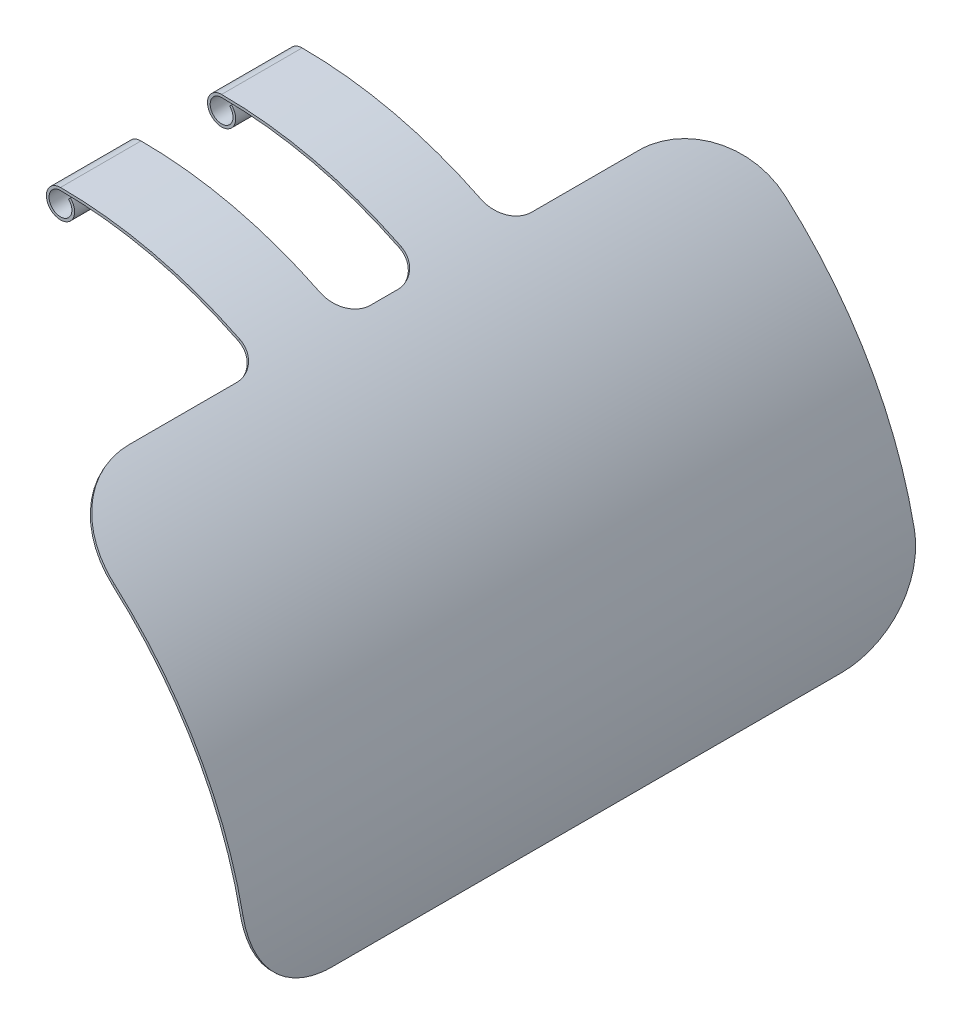
SolidWorks part; units mm, degrees
material "1.4301 (X5CrNi18-10)"
ref_plane "Front Plane" through (0, 0, 0) normal (0, 0, 1) x (1, 0, 0)
ref_plane "Top Plane" through (0, 0, 0) normal (0, 1, 0) x (1, 0, 0)
ref_plane "Right Plane" through (0, 0, 0) normal (1, 0, 0) x (0, 0, -1)
sketch "Sketch2" plane through (0, 0, 0) normal (0, 0, 1) x (1, 0, 0)
  line L0 (0, -55) -> (0, 55) construction
  line L1 (0, 0) -> (0, 175.478) construction
  line L2 (-60.0259, 0) -> (145.2452, 0) construction
  line L4 (0, 145.75) -> (4.6775, 150.4275) construction
  line L5 (3.0052, 148.7552) -> (3.7123, 149.4623)
  line L7 (0, 0) -> (136.1579, 0) construction
  line L8 (55, 0) -> (-55, 0) construction
  line L9 (150, 0) -> (151, 0)
  arc A0 (150, 0) -> (0, 150) centre (0, 0) ccw
  arc A1 (0, 150) -> (3.0052, 148.7552) centre (0, 145.75) ccw
  arc A2 (151, 0) -> (0, 151) centre (0, 0) ccw
  arc A3 (0, 151) -> (3.7123, 149.4623) centre (0, 145.75) ccw
  arc A4 (150, 0) -> (0, 150) centre (0, 0) ccw construction
  arc A5 (151, 0) -> (0, 151) centre (0, 0) ccw construction
  dimension "D1" = 300
  dimension "D2" = 8.5
  dimension "D3" = 45
  dimension "D5" = 0
  dimension "D4" = 1
extrude "Boss-Extrude1" add sketch "Sketch2" along normal mid plane 250
sketch "Sketch3" plane through (0, 0, 0) normal (0, 0, 1) x (1, 0, 0)
  line L0 (75, 129.9038) -> (75.5, 130.7698)
  line L1 (55, 0) -> (-55, 0) construction
  line L2 (150, 0) -> (151, 0)
  line L3 (3.7123, 149.4623) -> (3.0052, 148.7552)
  line L5 (3.7123, 149.4623) -> (3.0052, 148.7552)
  arc A4 (0, 150) -> (3.0052, 148.7552) centre (0, 145.75) ccw
  arc A5 (150, 0) -> (0, 150) centre (0, 0) ccw
  arc A6 (151, 0) -> (0, 151) centre (0, 0) ccw
  arc A7 (0, 151) -> (3.7123, 149.4623) centre (0, 145.75) ccw
  arc A8 (0, 150) -> (3.0052, 148.7552) centre (0, 145.75) ccw
  arc A9 (75, 129.9038) -> (0, 150) centre (0, 0) ccw
  arc A10 (75.5, 130.7698) -> (0, 151) centre (0, 0) ccw
  arc A11 (0, 151) -> (3.7123, 149.4623) centre (0, 145.75) ccw
  dimension "D2" = 60
  dimension "D1" = 0
extrude "Cut-Extrude1" cut sketch "Sketch3" against normal mid plane 30
sketch "Sketch4" plane through (0, 0, 125) normal (0, 0, 1) x (1, 0, 0)
  line L0 (75, 129.9038) -> (75.5, 130.7698)
  line L1 (55, 0) -> (-55, 0) construction
  line L2 (150, 0) -> (151, 0)
  line L3 (3.7123, 149.4623) -> (3.0052, 148.7552)
  line L5 (3.7123, 149.4623) -> (3.0052, 148.7552)
  arc A4 (0, 150) -> (3.0052, 148.7552) centre (0, 145.75) ccw
  arc A5 (150, 0) -> (0, 150) centre (0, 0) ccw
  arc A6 (151, 0) -> (0, 151) centre (0, 0) ccw
  arc A7 (0, 151) -> (3.7123, 149.4623) centre (0, 145.75) ccw
  arc A8 (0, 150) -> (3.0052, 148.7552) centre (0, 145.75) ccw
  arc A9 (75, 129.9038) -> (0, 150) centre (0, 0) ccw
  arc A10 (75.5, 130.7698) -> (0, 151) centre (0, 0) ccw
  arc A11 (0, 151) -> (3.7123, 149.4623) centre (0, 145.75) ccw
  dimension "D2" = 60
  dimension "D1" = 0
extrude "Cut-Extrude2" cut sketch "Sketch4" against normal blind 80
mirror "Mirror1" about plane through (0, 0, 0) normal (0, 0, 1) of "Cut-Extrude2"
fillet "Fillet1" radius 30 4 edges at (75.25, 130.3368, -125) (75.25, 130.3368, 125) (150.5, 0, -125) (150.5, 0, 125)
fillet "Fillet2" radius 10 4 edges at (75.25, 130.3368, -45) (75.25, 130.3368, 45) (75.25, 130.3368, 15) (75.25, 130.3368, -15)
